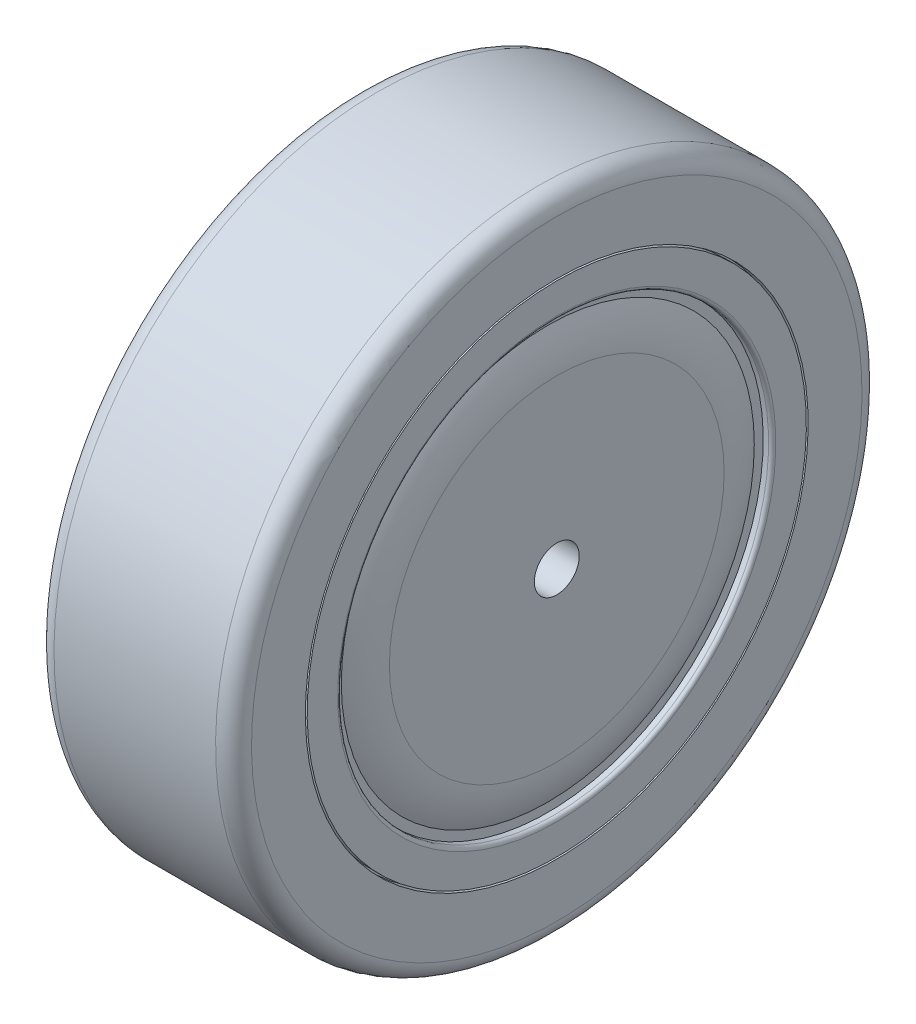
SolidWorks part; units mm, degrees
ref_plane "Plan de face" through (0, 0, 0) normal (0, 0, 1) x (1, 0, 0)
ref_plane "Plan de dessus" through (0, 0, 0) normal (0, 1, 0) x (1, 0, 0)
ref_plane "Plan de droite" through (0, 0, 0) normal (1, 0, 0) x (0, 0, -1)
sketch "Esquisse1" plane through (0, 0, 0) normal (0, 0, 1) x (1, 0, 0)
  line L2 (9, -36) -> (-9, -36)
  line L3 (11, -24) -> (10, -24)
  line L5 (11, -34) -> (11, -28)
  line L6 (11, -28) -> (10, -28)
  line L7 (10, -28) -> (10, -27.8)
  line L8 (10, -27.8) -> (11, -27.8)
  line L9 (11, -27.8) -> (11, -24)
  line L10 (0, 0) -> (0, -36) construction
  line L11 (11, 0) -> (-11, 0)
  line L12 (10, -24) -> (10, -23)
  line L13 (10, -23) -> (11, -23)
  line L14 (11, -23) -> (11, 0)
  line L15 (10, -24) -> (10, -27.8) construction
  line L16 (-10, -24) -> (-10, -27.8) construction
  line L17 (-11, -23) -> (-11, 0)
  line L18 (-10, -23) -> (-11, -23)
  line L19 (-10, -24) -> (-10, -23)
  line L20 (-11, -27.8) -> (-11, -24)
  line L21 (-10, -27.8) -> (-11, -27.8)
  line L22 (-10, -28) -> (-10, -27.8)
  line L23 (-11, -28) -> (-10, -28)
  line L24 (-11, -34) -> (-11, -28)
  line L25 (-11, -24) -> (-10, -24)
  arc A0 (11, -34) -> (9, -36) centre (9, -34) cw
  arc A1 (-11, -34) -> (-9, -36) centre (-9, -34) ccw
  point P4 (0, 0)
  dimension "D8" = 2
  dimension "D1" = 36
  dimension "D2" = 11
  dimension "D3" = 8
  dimension "D4" = 0.2
  dimension "D5" = 1
  dimension "D6" = 12
  dimension "D7" = 1
revolve "Révolution1" add sketch "Esquisse1" angle 360 about L11
sketch "Esquisse2" plane through (0, 0, 0) normal (-1, 0, 0) x (0, 0, 1)
  circle A0 centre (0, 0) radius 2.5
  dimension "D1" = 5
extrude "Enlèv. mat.-Extru.1" cut sketch "Esquisse2" against normal through all both and the other way through all
fillet "Fillet1" radius 10 2 edges at (-11, 23, 0) (11, 23, 0)
fillet "Fillet2" radius 0.4 2 edges at (-11, 24, 0) (11, 24, 0)
